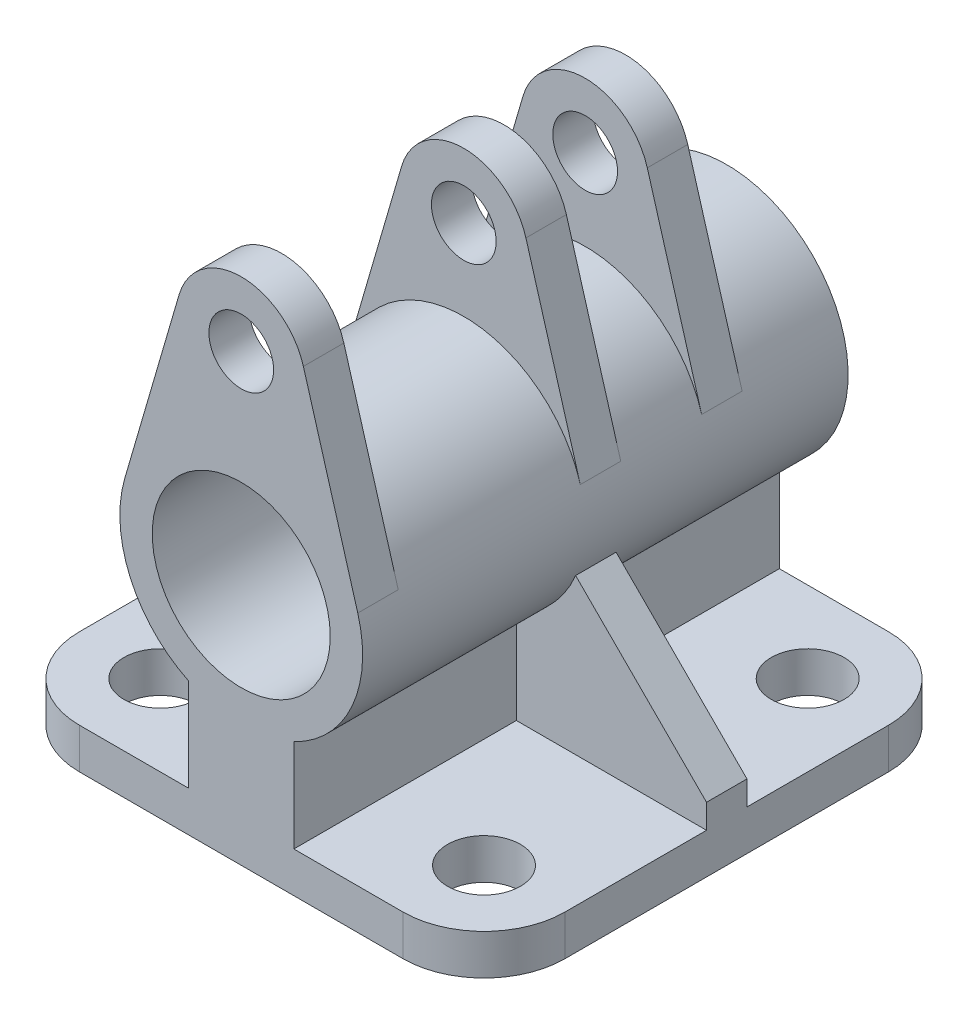
SolidWorks part; units mm, degrees
ref_plane "Спереди" through (0, 0, 0) normal (0, 0, 1) x (1, 0, 0)
ref_plane "Сверху" through (0, 0, 0) normal (0, 1, 0) x (1, 0, 0)
ref_plane "Справа" through (0, 0, 0) normal (1, 0, 0) x (0, 0, -1)
sketch "Эскиз1" plane through (0, 0, 0) normal (0, 0, 1) x (1, 0, 0)
  line L0 (0, 0) -> (0, -29.7354) construction
  line L1 (30, -30) -> (-30, -30)
  line L2 (30, -30) -> (30, -22)
  line L3 (30, -25) -> (6.5, -25)
  line L4 (30, -22) -> (13.8234, -5.8234)
  line L5 (6.5, -25) -> (6.5, -13.5185)
  line L6 (-6.5, -25) -> (-6.5, -13.5185)
  line L7 (-30, -22) -> (-13.8234, -5.8234)
  line L8 (-30, -25) -> (-6.5, -25)
  line L9 (-30, -30) -> (-30, -22)
  line L10 (-7.68, 27.24) -> (-14.4, 4.2)
  line L11 (7.68, 27.24) -> (14.4, 4.2)
  circle A0 centre (0, 0) radius 11
  circle A1 centre (0, 0) radius 15
  arc A2 (7.68, 27.24) -> (-7.68, 27.24) centre (0, 25) ccw
  circle A3 centre (0, 25) radius 4
  point P18 (0, -30)
  point P19 (0, 25)
  dimension "D1" = 22
  dimension "D2" = 30
  dimension "D9" = 16
  dimension "D10" = 8
  dimension "D3" = 30
  dimension "D4" = 8
  dimension "D5" = 30
  dimension "D6" = 5
  dimension "D7" = 45
  dimension "D8" = 6.5
  dimension "D11" = 55
extrude "Бобышка-Вытянуть1" add sketch "Эскиз1" along normal mid plane 60 contours A0 A1 | A1 L6 L8 L9 L1 L2 L3 L5 region at (0, -25.0787, 0) region at (10.5584, -10.0485, 0)
extrude "Бобышка-Вытянуть2" add sketch "Эскиз1<3>" along normal mid plane 5 contours L11 A2 L10 A1 A3 | A1 L5 L3 L2 L4 | A1 L7 L9 L8 L6 region at (16.4394, -18.1684, 0) region at (-16.4394, -18.1684, 0) region at (0, 20.665, 0)
sketch "Эскиз1<3>" plane through (0, 0, 0) normal (0, 0, 1) x (1, 0, 0) same geometry as "Эскиз1"
extrude "Бобышка-Вытянуть4" add sketch "Эскиз1<6>" along normal mid plane 5 from offset 15 contours L11 A2 L10 A1 A3 region at (0, 20.665, 0) offset against normal yes
sketch "Эскиз1<6>" plane through (0, 0, 0) normal (0, 0, 1) x (1, 0, 0) same geometry as "Эскиз1"
extrude "Бобышка-Вытянуть5" add sketch "Эскиз1<7>" against normal blind 5 from surface contours L11 A2 L10 A1 A3 region at (0, 20.665, 0) starting at face at (0, -19.8148, 30)
sketch "Эскиз1<7>" plane through (0, 0, 0) normal (0, 0, 1) x (1, 0, 0) same geometry as "Эскиз1"
sketch "Эскиз7" plane through (0, -30, 0) normal (0, -1, 0) x (1, 0, 0)
  line L0 (-30, 0) -> (30, 0) construction
  line L1 (-30, 30) -> (-30, -30) construction
  line L2 (30, 30) -> (30, -30) construction
  line L3 (0, 30) -> (0, -30) construction
  line L4 (30, 30) -> (-30, 30) construction
  line L5 (30, -30) -> (-30, -30) construction
  circle A0 centre (-20, 20) radius 4.5
  point P14 (18.8673, 18.3604)
  point P15 (0, 0)
  dimension "D1" = 9
  dimension "D2" = 20
  dimension "D3" = 20
extrude "Вырез-Вытянуть1" cut sketch "Эскиз7" against normal through all contours A0
mirror "Зеркальное отражение1" about plane through (0, 0, 0) normal (1, 0, 0) of "Вырез-Вытянуть1"
mirror "Зеркальное отражение2" about plane through (0, 0, 0) normal (0, 0, 1) of "Зеркальное отражение1"
fillet "Скругление1" radius 10 4 edges at (-30, -27.5, -30) (-30, -27.5, 30) (30, -27.5, -30) (30, -27.5, 30)
